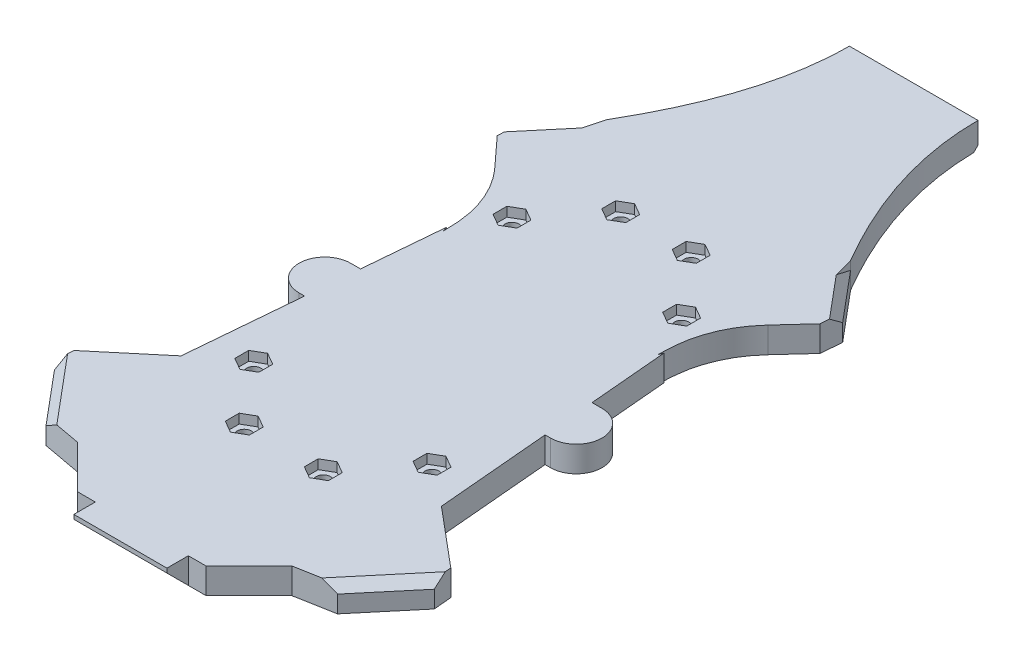
SolidWorks part; units mm, degrees
ref_plane "Front Plane" through (0, 0, 0) normal (0, 0, 1) x (1, 0, 0)
ref_plane "Top Plane" through (0, 0, 0) normal (0, 1, 0) x (1, 0, 0)
ref_plane "Right Plane" through (0, 0, 0) normal (1, 0, 0) x (0, 0, -1)
sketch "Sketch1" plane through (0, 0, 0) normal (0, 1, 0) x (1, 0, 0)
  line L1 (25, -90) -> (-25, -90)
  line L2 (25, -90) -> (25, 90)
  line L3 (25, 90) -> (-25, 90)
  line L4 (-25, -90) -> (-25, 90)
  line L5 (25, -90) -> (-25, 90) construction
  line L6 (25, 90) -> (-25, -90) construction
  point P0 (0, 0)
  dimension "D1" = 50
  dimension "D2" = 180
extrude "Boss-Extrude1" add sketch "Sketch1" along normal blind 6
sketch "Sketch2" plane through (0, 6, 0) normal (0, 1, 0) x (1, 0, 0)
  line L0 (0, -90) -> (0, -59.8277)
  line L1 (-25, -90) -> (25, -90) construction
sketch "Sketch3" plane through (0, 6, 0) normal (0, 1, 0) x (1, 0, 0)
  line L0 (-25, -90) -> (25, -90) construction
  line L1 (15.25, -33.25) -> (-15.25, -33.25)
  line L2 (15.25, -33.25) -> (15.25, -2.75)
  line L3 (15.25, -2.75) -> (-15.25, -2.75)
  line L4 (-15.25, -33.25) -> (-15.25, -2.75)
  line L5 (15.25, -33.25) -> (-15.25, -2.75) construction
  line L6 (15.25, -2.75) -> (-15.25, -33.25) construction
  line L7 (0, -18) -> (0, -90) construction
  point P0 (0, -18)
  dimension "D1" = 30.5
  dimension "D2" = 72
chamfer "Chamfer2" distance 10 angle 45 4 edges at (25, 3, -90) (-25, 3, -90) (-25, 3, 90) (25, 3, 90)
hole_wizard "Ø3.3 (3.3) Diameter Hole1" positions "Sketch7" profile "Sketch8" hole size "Ø3.3" standard "ANSI Metric" end condition through all
sketch "Sketch7" plane through (0, 6, 0) normal (0, 1, 0) x (1, 0, 0)
  line L2 (-25, 0) -> (25, 0) construction
  line L3 (-25, 80) -> (-25, -80) construction
  line L4 (25, -80) -> (25, 80) construction
  line L6 (0, 90) -> (0, -90) construction
  line L7 (15, 90) -> (-15, 90) construction
  line L8 (-15, -90) -> (15, -90) construction
  line L9 (9.2149, -56.8944) -> (20.7851, -43.1056) construction
  line L10 (15, -50) -> (22.6604, -56.4279) construction
  line L20 (8.2149, 29.8944) -> (19.7851, 16.1056) construction
  line L22 (14, 23) -> (21.6604, 29.4279) construction
  point P33 (9.2149, -56.8944)
  point P34 (20.7851, -43.1056)
  point P46 (-9.2149, -56.8944)
  point P47 (-20.7851, -43.1056)
  point P48 (19.7851, 16.1056)
  point P49 (8.2149, 29.8944)
  point P112 (-8.2149, 29.8944)
  point P113 (-19.7851, 16.1056)
  dimension "D1" = 50
  dimension "D2" = 10
  dimension "D3" = 50
  dimension "D4" = 18
  dimension "D5" = 10
  dimension "D7" = 50
  dimension "D8" = 11
  dimension "D9" = 23
sketch "Sketch8" plane through (-19.7851, 6, -16.1056) normal (1, 0, 0) x (0, 0, 1)
  line L0 (0, 0) -> (0, 6)
  line L1 (0, 6) -> (1.65, 6)
  line L2 (1.65, 6) -> (1.65, 0)
  line L5 (1.65, 0) -> (0, 0)
  line L11 (0, -6.35) -> (0, 107.95) construction
  dimension "Thru Hole Dia." = 3.3
  dimension "Thru Hole Depth" = 6
sketch "Sketch52" plane through (0, 6, 0) normal (0, 1, 0) x (1, 0, 0)
  line L0 (0, 28.8816) -> (0, 18.7178) construction
  line L1 (8.2149, 29.8944) -> (19.7851, 16.1056) construction
  line L2 (14, 23) -> (17.7179, 26.1197) construction
  line L4 (25, -80) -> (25, 80) construction
  line L7 (40, 33.0679) -> (31.85, 24.1738)
  line L8 (31.85, 24.1738) -> (25, 5.3535)
  line L10 (25, 59.657) -> (25, 5.3535)
  line L16 (28.4298, 46.8567) -> (40, 33.0679)
  line L17 (-28.4298, 46.8567) -> (-40, 33.0679)
  line L18 (-25, 59.657) -> (-28.4298, 46.8567)
  line L19 (-25, 59.657) -> (-25, 5.3535)
  line L20 (-31.85, 24.1738) -> (-25, 5.3535)
  line L21 (-40, 33.0679) -> (-31.85, 24.1738)
  line L22 (28.4298, 46.8567) -> (25, 59.657)
  line L23 (25, -80) -> (25, 80) construction
  point P25 (34.2149, 39.9623)
  dimension "D1" = 18
  dimension "D2" = 20
  dimension "D3" = 15
  dimension "D4" = 6.85
  dimension "D5" = 15
  dimension "D6" = 97.5
extrude "Boss-Extrude3" add sketch "Sketch52" against normal through all
sketch "Sketch11" plane through (0, 6, 0) normal (0, 1, 0) x (1, 0, 0)
  line L1 (23.5851, -44.7222) -> (23.5851, -41.489)
  line L2 (23.5851, -41.489) -> (20.7851, -39.8724)
  line L3 (20.7851, -39.8724) -> (17.9851, -41.489)
  line L4 (17.9851, -41.489) -> (17.9851, -44.7222)
  line L5 (17.9851, -44.7222) -> (20.7851, -46.3388)
  line L6 (20.7851, -46.3388) -> (23.5851, -44.7222)
  line L15 (0, 14.9971) -> (0, -9.9212) construction
  line L16 (9.2149, -60.1276) -> (12.0149, -58.511)
  line L17 (12.0149, -58.511) -> (12.0149, -55.2778)
  line L18 (12.0149, -55.2778) -> (9.2149, -53.6612)
  line L19 (9.2149, -53.6612) -> (6.4149, -55.2778)
  line L20 (6.4149, -55.2778) -> (6.4149, -58.511)
  line L21 (6.4149, -58.511) -> (9.2149, -60.1276)
  line L22 (-17.2929, 0) -> (15.5262, 0) construction
  line L23 (-6.4149, -58.511) -> (-9.2149, -60.1276)
  line L24 (-6.4149, -55.2778) -> (-6.4149, -58.511)
  line L25 (-9.2149, -53.6612) -> (-6.4149, -55.2778)
  line L26 (-12.0149, -55.2778) -> (-9.2149, -53.6612)
  line L27 (-12.0149, -58.511) -> (-12.0149, -55.2778)
  line L28 (-9.2149, -60.1276) -> (-12.0149, -58.511)
  line L35 (-20.7851, -46.3388) -> (-23.5851, -44.7222)
  line L36 (-17.9851, -44.7222) -> (-20.7851, -46.3388)
  line L37 (-17.9851, -41.489) -> (-17.9851, -44.7222)
  line L38 (-20.7851, -39.8724) -> (-17.9851, -41.489)
  line L39 (-23.5851, -41.489) -> (-20.7851, -39.8724)
  line L40 (-23.5851, -44.7222) -> (-23.5851, -41.489)
  line L88 (19.7851, 12.8724) -> (22.5851, 14.489)
  line L89 (22.5851, 14.489) -> (22.5851, 17.7222)
  line L90 (22.5851, 17.7222) -> (19.7851, 19.3388)
  line L91 (19.7851, 19.3388) -> (16.9851, 17.7222)
  line L92 (16.9851, 17.7222) -> (16.9851, 14.489)
  line L93 (16.9851, 14.489) -> (19.7851, 12.8724)
  line L94 (8.2149, 26.6612) -> (11.0149, 28.2778)
  line L95 (11.0149, 28.2778) -> (11.0149, 31.511)
  line L96 (11.0149, 31.511) -> (8.2149, 33.1276)
  line L97 (8.2149, 33.1276) -> (5.4149, 31.511)
  line L98 (5.4149, 31.511) -> (5.4149, 28.2778)
  line L99 (5.4149, 28.2778) -> (8.2149, 26.6612)
  line L100 (-19.7851, 12.8724) -> (-16.9851, 14.489)
  line L101 (-16.9851, 14.489) -> (-16.9851, 17.7222)
  line L102 (-16.9851, 17.7222) -> (-19.7851, 19.3388)
  line L103 (-19.7851, 19.3388) -> (-22.5851, 17.7222)
  line L104 (-22.5851, 17.7222) -> (-22.5851, 14.489)
  line L105 (-22.5851, 14.489) -> (-19.7851, 12.8724)
  line L106 (-8.2149, 26.6612) -> (-5.4149, 28.2778)
  line L107 (-5.4149, 28.2778) -> (-5.4149, 31.511)
  line L108 (-5.4149, 31.511) -> (-8.2149, 33.1276)
  line L109 (-8.2149, 33.1276) -> (-11.0149, 31.511)
  line L110 (-11.0149, 31.511) -> (-11.0149, 28.2778)
  line L111 (-11.0149, 28.2778) -> (-8.2149, 26.6612)
  circle A0 centre (20.7851, -43.1056) radius 2.8 construction
  circle A2 centre (9.2149, -56.8944) radius 2.8 construction
  circle A3 centre (-9.2149, -56.8944) radius 2.8 construction
  circle A5 centre (-20.7851, -43.1056) radius 2.8 construction
  circle A6 centre (-19.7851, 16.1056) radius 2.8 construction
  circle A7 centre (19.7851, 16.1056) radius 2.8 construction
  circle A8 centre (-8.2149, 29.8944) radius 2.8 construction
  circle A9 centre (8.2149, 29.8944) radius 2.8 construction
  dimension "D1" = 5.6
extrude "Cut-Extrude3" cut sketch "Sketch11" against normal blind 2.2
sketch "Sketch53" plane through (0, 6, 0) normal (0, 1, 0) x (1, 0, 0)
  line L0 (20.7851, -43.1056) -> (9.2149, -56.8944) construction
  line L1 (15, -50) -> (15.3372, -50.2829) construction
  line L3 (25, -80) -> (25, 5.3535) construction
  line L5 (25, -45.9896) -> (25, -80)
  line L7 (34, -78.3443) -> (46.213, -63.7894)
  line L8 (46.213, -63.7894) -> (25, -45.9896)
  line L9 (0, -71.0769) -> (0, -64.6229) construction
  line L10 (-46.213, -63.7894) -> (-25, -45.9896)
  line L11 (-34, -78.3443) -> (-46.213, -63.7894)
  line L12 (-25, -80) -> (-34, -78.3443)
  line L13 (-25, -45.9896) -> (-25, -80)
  line L14 (34, -78.3443) -> (25, -80)
  point P13 (40.1065, -71.0668)
  dimension "D1" = 9
  dimension "D2" = 19
extrude "Boss-Extrude4" add sketch "Sketch53" against normal through all
chamfer "Chamfer14" distance 2 angle 45 2 edges at (-40.1065, 6, 71.0668) (40.1065, 6, 71.0668)
chamfer "Chamfer16" distance 7 angle 45 2 edges at (25, 3, 45.9896) (-25, 3, 45.9896) first distance on face at (37.4214, 3.2, 56.4124) first distance on face at (-37.4214, 3.2, 56.4124)
chamfer "Chamfer17" distance 2 angle 45 2 edges at (-34.2149, 6, -39.9623) (34.2149, 6, -39.9623)
sketch "Sketch59" plane through (0, 6, 0) normal (0, 1, 0) x (1, 0, 0)
  line L1 (-10.85, -90) -> (10.85, -90)
  line L2 (-10.85, -90) -> (-10.85, -95)
  line L3 (-10.85, -95) -> (10.85, -95)
  line L4 (10.85, -90) -> (10.85, -95)
  dimension "D1" = 5
extrude "Boss-Extrude5" add sketch "Sketch59" against normal through all
chamfer "Chamfer19" distance 5 angle 45 1 edges at (0, 0, 95)
sketch "Sketch61" plane through (0, 0, 0) normal (0, -1, 0) x (1, 0, 0)
  line L0 (25, -59.657) -> (15, -90)
  line L3 (15, -90) -> (25, -80)
  line L4 (25, -80) -> (25, -59.657)
  line L5 (0, -69.8334) -> (0, -62.3475) construction
  line L6 (-25, -80) -> (-25, -59.657)
  line L7 (-15, -90) -> (-25, -80)
  line L8 (-25, -59.657) -> (-15, -90)
extrude "Cut-Extrude28" cut sketch "Sketch61" against normal through all
chamfer "Chamfer20" distance 3 angle 45 4 edges at (-40, 2, -33.0679) (40, 2, -33.0679) (-46.213, 2, 63.7894) (46.213, 2, 63.7894) first distance on face at (-36.4674, 3.2, -29.2128) first distance on face at (34.2149, 2, -39.9623) first distance on face at (-40.1065, 2, 71.0668) first distance on face at (39.5663, 3.2, 58.2122)
sketch "Sketch62" plane through (0, 6, 0) normal (0, 1, 0) x (1, 0, 0)
  line L0 (0, 67.8456) -> (0, 57.6028) construction
  line L1 (29.6547, 42.2856) -> (25, 59.657) construction
  line L2 (28.4298, 46.8567) -> (38.0716, 35.3661) construction
  line L4 (15, 90) -> (25, 59.657)
  line L5 (25, 59.657) -> (28.4298, 46.8567)
  line L6 (15, 90) -> (28.4298, 46.8567) construction
  line L7 (21.7149, 68.4284) -> (18.8505, 67.5367) construction
  line L8 (-25, 59.657) -> (-28.4298, 46.8567)
  line L9 (-15, 90) -> (-25, 59.657)
  line L10 (15, 90) -> (-15, 90) construction
  spline S0 degree 3 poles (28.4298, 46.8567) (20.7913, 59.9052) (15, 74.5738) (15, 90) knots 0 0 0 0 1 1 1 1
  spline S1 degree 3 poles (-28.4298, 46.8567) (-20.7913, 59.9052) (-15, 74.5738) (-15, 90) knots 0 0 0 0 1 1 1 1
  dimension "D1" = 3
extrude "Cut-Extrude29" cut sketch "Sketch62" against normal through all
chamfer "Chamfer24" distance 1 angle 45 1 edges at (0, 0, -90)
sketch "Sketch64" plane through (0, 6, 0) normal (0, 1, 0) x (1, 0, 0)
  line L1 (31.85, 24.1738) -> (37.6458, 30.4988) construction
  line L4 (28.6172, 15.2916) -> (26.7378, 15.9757) construction
  line L5 (25.3843, 6.4095) -> (31.85, 24.1738) construction
  line L6 (31.85, 24.1738) -> (25, 5.3535)
  line L7 (0, 11.3453) -> (0, 14.5667) construction
  line L8 (-28.6172, 15.2916) -> (-26.7378, 15.9757) construction
  line L9 (-31.85, 24.1738) -> (-25, 5.3535)
  spline S0 degree 3 poles (25, 5.3535) (25, 9.9392) (26.1038, 15.683) (29.2762, 21.3649) (31.85, 24.1738) knots 0 0 0 0 0.526974 1 1 1 1
  spline S1 degree 3 poles (-25, 5.3535) (-25, 9.9392) (-26.1038, 15.683) (-29.2762, 21.3649) (-31.85, 24.1738) knots 0 0 0 0 0.526974 1 1 1 1
  dimension "D1" = 2
extrude "Cut-Extrude31" cut sketch "Sketch64" against normal through all
sketch "Sketch66" plane through (0, 6, 0) normal (0, 1, 0) x (1, 0, 0)
  line L0 (29.3209, 35.8558) -> (29.3209, -18) construction
  line L1 (15.25, -2.75) -> (15.25, -33.25) construction
  line L7 (0, -18) -> (0, -26.2369) construction
  line L12 (15.25, -18) -> (29.3209, -18) construction
  line L13 (29.3209, -12) -> (25, -12)
  line L15 (25, -12) -> (25, -13.8371)
  line L16 (25, -24) -> (25, -22.1629)
  line L17 (29.3209, -24) -> (25, -24)
  line L18 (-29.3209, -24) -> (-25, -24)
  line L19 (-25, -24) -> (-25, -22.1629)
  line L20 (-25, -12) -> (-25, -13.8371)
  line L21 (-29.3209, -12) -> (-25, -12)
  circle A0 centre (29.3209, -18) radius 6
  circle A1 centre (-29.3209, -18) radius 6
  dimension "D1" = 12
extrude "Boss-Extrude6" add sketch "Sketch66" against normal blind 6 contours A0 | A0 L13 L15 | A0 L16 L17 | A1 | L21 A1 L20 | L19 A1 L18 region at (26.0444, 6, 12.5329) region at (29.3209, 6, 18) region at (26.0444, 6, 23.4671) region at (-26.0444, 6, 23.4671) region at (-29.3209, 6, 18) region at (-26.0444, 6, 12.5329)
